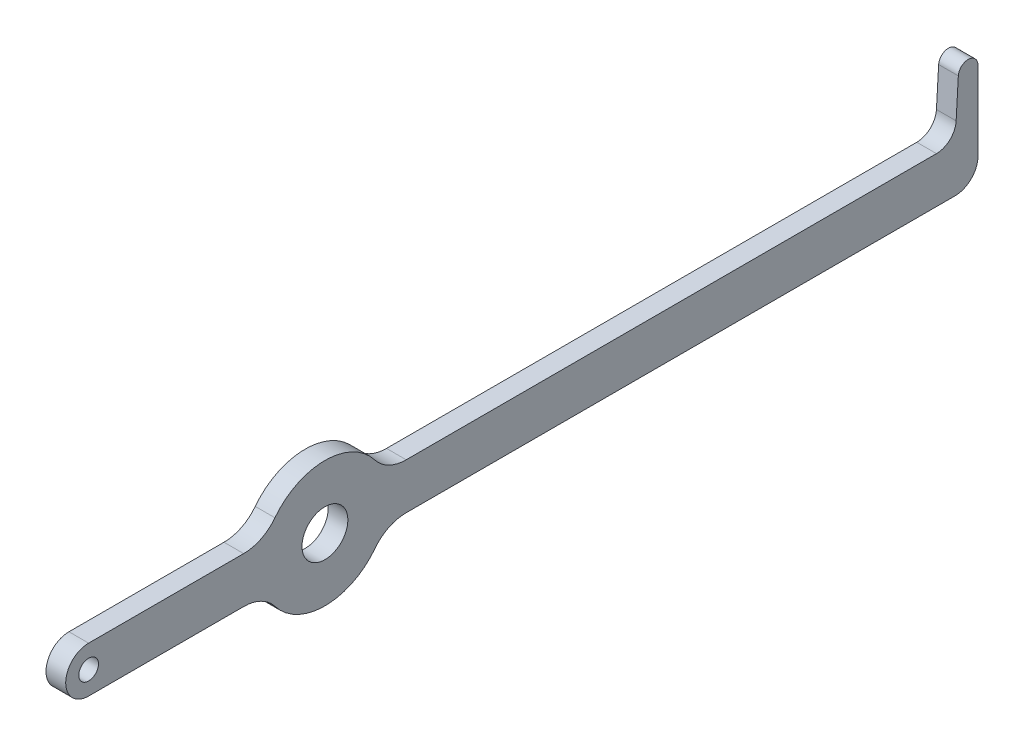
SolidWorks part; units mm, degrees
material "Balsa"
ref_plane "Front Plane" through (0, 0, 0) normal (0, 0, 1) x (1, 0, 0)
ref_plane "Top Plane" through (0, 0, 0) normal (0, 1, 0) x (1, 0, 0)
ref_plane "Right Plane" through (0, 0, 0) normal (1, 0, 0) x (0, 0, -1)
sketch "Sketch1" plane through (0, 0, 0) normal (1, 0, 0) x (0, 0, -1)
  line L0 (0, 0) -> (-38.1, 0) construction
  line L1 (0, -3.698) -> (-38.1, -3.698)
  line L2 (0, 3.698) -> (-38.1, 3.698)
  line L3 (0, 0) -> (101.6, 0) construction
  line L4 (0, 3.698) -> (101.6, 3.698)
  line L5 (0, -3.698) -> (101.6, -3.698)
  circle A0 centre (0, 0) radius 10.16
  arc A1 (0, -3.698) -> (0, 3.698) centre (0, 0) ccw
  arc A2 (-38.1, 3.698) -> (-38.1, -3.698) centre (-38.1, 0) ccw
  arc A3 (0, 3.698) -> (0, -3.698) centre (0, 0) ccw
  arc A4 (101.6, -3.698) -> (101.6, 3.698) centre (101.6, 0) ccw
  point P4 (-19.05, 0)
  point P9 (50.8, 0)
  dimension "D3" = 20.32
  dimension "D1" = 38.1
  dimension "D2" = 101.6
extrude "Boss-Extrude1" add sketch "Sketch1" along normal mid plane 3.175 contours L2 A2 L1 A0 | A3 L2 A0 L1 | L4 A0 L2 | L1 A0 L5 | A1 L5 A0 L4 | L5 A4 L4 A0 region at (0, -6.3695, 0) region at (0, 0, -6.3723) region at (0, 0, 6.3723) region at (0, 0, 25.478) region at (0, 0, -57.2211) region at (0, 6.3695, 0)
fillet "Fillet1" radius 6.35 4 edges at (0, 3.698, -9.4631) (0, -3.698, -9.4631) (0, -3.698, 9.4631) (0, 3.698, 9.4631)
sketch "Sketch2" plane through (0, 0, 0) normal (1, 0, 0) x (0, 0, -1)
  line L0 (105.298, 0) -> (105.298, 12.7)
  line L1 (13.1003, 3.698) -> (101.6, 3.698) construction
  line L4 (101.6, 3.698) -> (102.1257, 12.7916)
  arc A0 (101.6, -3.698) -> (101.6, 3.698) centre (101.6, 0) ccw construction
  arc A2 (105.298, 12.7) -> (102.1257, 12.7916) centre (103.7105, 12.7) ccw
  arc A3 (105.298, 0) -> (101.6, 3.698) centre (101.6, 0) ccw
  dimension "D2" = 1.5875
  dimension "D1" = 12.7
extrude "Boss-Extrude2" add sketch "Sketch2" against normal mid plane 3.175
fillet "Fillet2" radius 3.175 1 edges at (0, 3.698, -101.6)
sketch "Sketch3" plane through (1.5875, 0, 0) normal (1, 0, 0) x (0, 0, -1)
  circle A0 centre (-38.1, 0) radius 1.5875
  dimension "D1" = 3.175
extrude "Cut-Extrude1" cut sketch "Sketch3" against normal through all both and the other way through all
